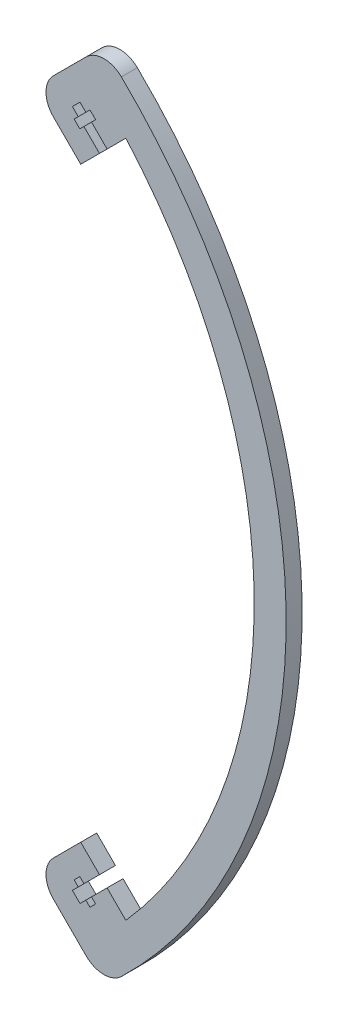
SolidWorks part; units mm, degrees
ref_plane "Front Plane" through (0, 0, 0) normal (0, 0, 1) x (1, 0, 0)
ref_plane "Top Plane" through (0, 0, 0) normal (0, 1, 0) x (1, 0, 0)
ref_plane "Right Plane" through (0, 0, 0) normal (1, 0, 0) x (0, 0, -1)
sketch "Sketch1" plane through (0, 0, 0) normal (0, 0, 1) x (1, 0, 0)
  line L0 (143.3604, 116.9193) -> (134.3442, 107.9031)
  line L1 (143.3604, -160.8213) -> (134.3442, -151.805)
  line L2 (143.3604, -160.8213) -> (128.1057, -145.5666) construction
  line L3 (128.1057, 101.6647) -> (143.3604, 116.9193) construction
  arc A0 (143.3604, 116.9193) -> (143.3604, -160.8213) centre (-21.951, -21.951) cw
  arc A1 (134.3442, 107.9031) -> (134.3442, -151.805) centre (-21.951, -21.951) cw
  arc A2 (143.3604, 116.9193) -> (131.0145, 130.4116) centre (-21.951, -21.951) ccw construction
  dimension "D1" = 12.7
extrude "Arc Extrusion" add sketch "Sketch1" along normal blind 6.35
ref_plane "Clothes Line Center Plane" through (0, -21.951, 0) normal (0, 1, 0) x (1, 0, 0)
sketch "Sketch4" plane through (0, 0, 6.35) normal (0, 0, 1) x (1, 0, 0)
  line L0 (134.3442, -151.805) -> (143.3604, -160.8213)
  line L1 (139.4438, -165.8849) -> (130.4636, -156.9046) construction
  line L2 (105.6551, -132.0962) -> (123.6156, -150.0567) construction
  line L3 (139.194, -165.6351) -> (112.2532, -138.6943)
  line L4 (112.2532, -138.6943) -> (94.2927, -156.6548)
  line L5 (94.2927, -156.6548) -> (121.204, -183.5661)
  arc A0 (143.3604, -160.8213) -> (139.194, -165.6351) centre (-21.951, -21.951) cw
  arc A1 (134.3442, -151.805) -> (130.1981, -156.6392) centre (-21.951, -21.951) cw
  arc A2 (139.194, -165.6351) -> (121.204, -183.5661) centre (-21.951, -21.951) cw
  arc A3 (134.3442, -151.805) -> (134.3442, 107.9031) centre (-21.951, -21.951) ccw construction
  arc A4 (143.3604, -160.8213) -> (143.3604, 116.9193) centre (-21.951, -21.951) ccw construction
  arc A5 (-192.6342, 110.2612) -> (-196.6177, 104.9519) centre (-21.951, -21.951) ccw construction
  line M8 (134.3442, -151.805) -> (143.3604, -160.8213)
  dimension "D1" = 25.4
  dimension "D2" = 38.1
extrude "Mount to V Funnel" add sketch "Sketch4" against normal up to surface (6.35 mm away) contours A1 L3 A0 M8 | A2 L3 L4 L5 region at (136.7864, -158.7357, 6.35) region at (116.8258, -161.2242, 6.35) up to face at (163.2257, -21.951, 0)
sketch "Sketch5" plane through (0, 0, 6.35) normal (0, 0, 1) x (1, 0, 0)
  line L0 (121.2256, -147.6667) -> (103.2651, -165.6272) construction
  line L1 (130.1981, -156.6392) -> (112.2532, -138.6943) construction
  line L2 (94.2927, -156.6548) -> (121.204, -183.5661) construction
  line L3 (130.1981, -156.6392) -> (112.2376, -174.5997)
  line L4 (112.2532, -138.6943) -> (94.2927, -156.6548) construction
  line B0 (122.7343, -149.1754) -> (119.717, -146.158)
  line B1 (111.2755, -154.5995) -> (109.6411, -152.9651)
  line B2 (109.6411, -152.9651) -> (111.8862, -150.72)
  line B3 (111.8862, -150.72) -> (113.5206, -152.3544)
  line B4 (113.5206, -152.3544) -> (119.717, -146.158)
  line B5 (111.2755, -154.5995) -> (108.9406, -156.9344)
  line B6 (108.9406, -156.9344) -> (111.958, -159.9517)
  line B7 (114.2929, -157.6169) -> (111.958, -159.9517)
  line B8 (116.5379, -155.3718) -> (122.7343, -149.1754)
  line B9 (118.1723, -157.0062) -> (116.5379, -155.3718)
  line B10 (115.9273, -159.2513) -> (118.1723, -157.0062)
  line B11 (114.2929, -157.6169) -> (115.9273, -159.2513)
  line M9 (130.1981, -156.6392) -> (112.2532, -138.6943)
sketch_block_instance "TSlot-1"
sketch_block "TSlot" parameters "D1"=3.302, "D2"=3.175
extrude "T Slot Hole" cut sketch "Sketch5" against normal through all contours L0 B6 B7 B11 B10 B9 B8 M9 | L0 B0 B4 B3 B2 B1 B5 B6 region at (116.5257, -154.4541, 6.35) region at (114.4382, -152.3667, 6.35)
mirror "Mount and T Slot Mirror" about plane through (0, -21.951, 0) normal (0, 1, 0) of "Mount to V Funnel", "T Slot Hole"
fillet "Mount Fillets" radius 10 4 edges at (94.2927, -156.6548, 3.175) (121.204, -183.5661, 3.175) (94.2927, 112.7529, 3.175) (121.204, 139.6642, 3.175)
